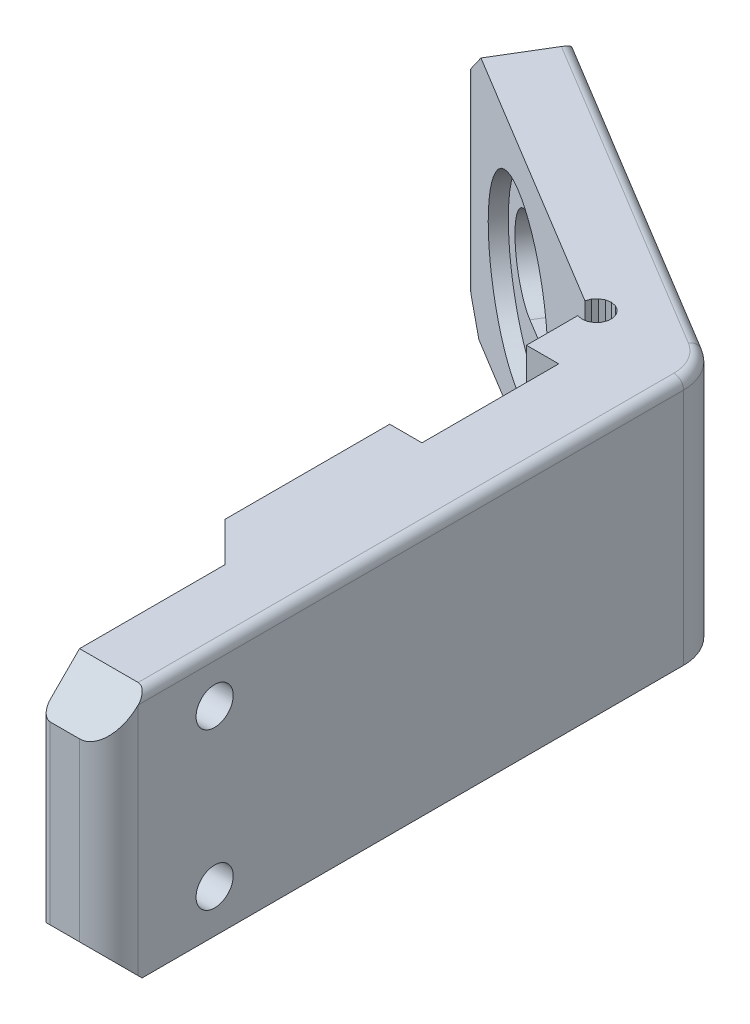
SolidWorks part; units mm, degrees
ref_plane "Front Plane" through (0, 0, 0) normal (0, 0, 1) x (1, 0, 0)
ref_plane "Top Plane" through (0, 0, 0) normal (0, 1, 0) x (1, 0, 0)
ref_plane "Right Plane" through (0, 0, 0) normal (1, 0, 0) x (0, 0, -1)
ref_plane "PY -20.700" through (0, -20.7, 0) normal (0, 1, 0) x (1, 0, 0)
sketch "leg and pad sketch" plane through (0, -20.7, 0) normal (0, 1, 0) x (1, 0, 0)
  line L0 (-0.5513, 30.3327) -> (-0.3673, 30.8194)
  line L1 (-0.3673, 30.8194) -> (-0.028, 31.2139)
  line L2 (-0.028, 31.2139) -> (0.4256, 31.4688)
  line L3 (0.4256, 31.4688) -> (0.939, 31.5534)
  line L4 (0.939, 31.5534) -> (1.4504, 31.4576)
  line L5 (1.4504, 31.4576) -> (1.8983, 31.1928)
  line L6 (1.8983, 31.1928) -> (2.2288, 30.7909)
  line L7 (2.2288, 30.7909) -> (2.4021, 30.3003)
  line L8 (2.4021, 30.3003) -> (2.3973, 29.78)
  line L9 (2.3973, 29.78) -> (2.2152, 29.2926)
  line L10 (2.2152, 29.2926) -> (1.8775, 28.8968)
  line L11 (1.8775, 28.8968) -> (1.4248, 28.6402)
  line L12 (1.4248, 28.6402) -> (0.9118, 28.5536)
  line L13 (0.9118, 28.5536) -> (0.4, 28.6475)
  line L14 (0.4, 28.6475) -> (0.4, -7.48)
  line L15 (0.4, -7.48) -> (4.42, -11.5)
  line L16 (4.42, -11.5) -> (4.42, -30.37)
  line L17 (4.42, -30.37) -> (11.42, -30.37)
  line L18 (11.42, -30.37) -> (11.42, 31.2838)
  line L19 (11.42, 31.2838) -> (-27.2048, 54.5947)
  line L20 (-27.2048, 54.5947) -> (-30.8218, 48.6015)
  line L21 (-30.8218, 48.6015) -> (-0.5513, 30.3327)
extrude "leg and pad" add sketch "leg and pad sketch" along normal mid plane 26
ref_plane "PX 1.350" through (1.35, 0, 0) normal (1, 0, 0) x (0, 0, -1)
sketch "screw head relief sketch" plane through (1.35, 0, 0) normal (1, 0, 0) x (0, 0, -1)
  line L0 (23.4, -12.7) -> (23.4, -6.7)
  line L1 (23.4, -6.7) -> (9.4, -6.7)
  line L2 (9.4, -6.7) -> (9.4, -12.7)
  line L3 (9.4, -12.7) -> (23.4, -12.7)
extrude "screw head relief" cut sketch "screw head relief sketch" against normal mid plane 4.7
sketch "insert flange relief sketch" plane through (0, -20.7, 0) normal (0, 1, 0) x (1, 0, 0)
  line L0 (-18.3249, 39.8914) -> (-17.0331, 42.0318)
  line L1 (-17.0331, 42.0318) -> (-9.3276, 37.3814)
  line L2 (-9.3276, 37.3814) -> (-10.6194, 35.241)
  line L3 (-10.6194, 35.241) -> (-18.3249, 39.8914)
revolve "insert flange relief" cut sketch "insert flange relief sketch" angle 360 about L0
sketch "M6 slot end 1 sketch" plane through (0, -20.7, 0) normal (0, 1, 0) x (1, 0, 0)
  line L0 (-20.4653, 41.1832) -> (-15.8149, 48.8886)
  line L1 (-15.8149, 48.8886) -> (-11.9621, 46.5634)
  line L2 (-11.9621, 46.5634) -> (-16.6125, 38.858)
  line L3 (-16.6125, 38.858) -> (-20.4653, 41.1832)
revolve "M6 slot end 1" cut sketch "M6 slot end 1 sketch" angle 360 about L0
sketch "M6 slot end 2 sketch" plane through (0, -20.7, 0) normal (0, 1, 0) x (1, 0, 0)
  line L0 (-16.1845, 38.5996) -> (-11.5341, 46.3051)
  line L1 (-11.5341, 46.3051) -> (-7.6813, 43.9799)
  line L2 (-7.6813, 43.9799) -> (-12.3317, 36.2744)
  line L3 (-12.3317, 36.2744) -> (-16.1845, 38.5996)
revolve "M6 slot end 2" cut sketch "M6 slot end 2 sketch" angle 360 about L0
sketch "M6 slot middle sketch" plane through (0, -20.7, 0) normal (0, 1, 0) x (1, 0, 0)
  line L0 (-16.1845, 38.5996) -> (-20.4653, 41.1832)
  line L1 (-20.4653, 41.1832) -> (-15.8149, 48.8886)
  line L2 (-15.8149, 48.8886) -> (-11.5341, 46.3051)
  line L3 (-11.5341, 46.3051) -> (-16.1845, 38.5996)
extrude "M6 slot middle" cut sketch "M6 slot middle sketch" against normal mid plane 9
ref_plane "PX 7.920" through (7.92, 0, 0) normal (1, 0, 0) x (0, 0, -1)
sketch "screw holes sketch" plane through (7.92, 0, 0) normal (1, 0, 0) x (0, 0, -1)
  circle A0 centre (-19.54, -28.7) radius 1.9
  circle A1 centre (-19.54, -12.7) radius 1.9
extrude "screw holes" cut sketch "screw holes sketch" against normal mid plane 9
chamfer "leg top corners" distance 4 angle 45 2 edges at (7.92, -7.7, 30.37) (7.92, -33.7, 30.37) tangent propagation no
chamfer "pad end corners" distance 4 angle 45 2 edges at (-29.0133, -7.7, -51.5981) (-29.0133, -33.7, -51.5981) tangent propagation no
fillet "outside of the bend" radius 5 1 edges at (11.42, -20.7, -31.2838) tangent propagation no
fillet "leg top outer edge" radius 3 1 edges at (11.42, -20.7, 30.37) tangent propagation no
fillet "pad end outer edge" radius 3 1 edges at (-27.2048, -20.7, -54.5947) tangent propagation no
fillet "leg top inner edge" radius 1 1 edges at (4.42, -20.7, 30.37) tangent propagation no
fillet "pad end inner edge" radius 1 1 edges at (-30.8218, -20.7, -48.6015) tangent propagation no
chamfer "bed face chamfer" distance 0.6 angle 45 6 edges at (-13.9742, -33.7, -38.4337) (-7.3883, -33.7, -42.635) (4.42, -33.7, 18.935) (0.4, -33.7, -10.5837) (10.7742, -33.7, -30.9193) (11.42, -33.7, -1.0457)
fillet "top face edge" radius 1 3 edges at (-7.3883, -7.7, -42.635) (10.7742, -7.7, -30.9193) (11.42, -7.7, -1.0457)
equation "\"diffL\"= 608.8mm"
equation "\"diffW\"= 329.4mm"
equation "\"diffT\"= 2.9mm"
equation "\"chanSlotW\"= 12.9mm"
equation "\"chanSlotDepth\"= 11.13mm"
equation "\"chanFloor\"= 1.57mm"
equation "\"chanLeg\"= 12.7mm"
equation "\"lightL\"= 605mm"
equation "\"lightW\"= 331mm"
equation "\"lightH\"= 92mm"
equation "\"lightSideFlat\"= 30mm"
equation "\"lightSlopeLen\"= 33.1mm"
equation "\"lightWingDepth\"= 47.9mm"
equation "\"lightWingFlat\"= 90.2mm"
equation "\"lightChanW\"= 99.6mm"
equation "\"lightChanStand\"= 44.1mm"
equation "\"insFlangeD\"= 12.3mm"
equation "\"insFromEnd\"= 20.7mm"
equation "\"insUpSlope\"= 20.8mm"
equation "\"gaugeH\"= 10mm"
equation "\"gaugeStepLen\"= 14mm"
equation "\"gaugeStepW0\"= 13.1mm"
equation "\"gaugeStepDW\"= 0.2mm"
equation "\"gaugeSteps\"= 5mm"
equation "\"gaugeHandleLen\"= 30mm"
equation "\"gaugeHandleW\"= 24mm"
equation "\"gaugeSlot0\"= 3mm"
equation "\"gaugeSlotD\"= 0.1mm"
equation "\"gaugeSlotDepth\"= 8mm"
equation "\"gap\"= 25.4mm"
equation "\"edgeL\"= 1mm"
equation "\"edgeW\"= 0.75mm"
equation "\"proud\"= 1.5mm"
equation "\"seatClr\"= 0.15mm"
equation "\"tongueClrZ\"= 0.1mm"
equation "\"tongueClrX\"= 0.25mm"
equation "\"tongueLen\"= 30mm"
equation "\"armSide\"= 45mm"
equation "\"armEnd\"= 20mm"
equation "\"cornerCham\"= 3mm"
equation "\"brkW\"= 26mm"
equation "\"brkT\"= 7mm"
equation "\"brkSeatClr\"= 0.2mm"
equation "\"brkScrewSpan\"= 16mm"
equation "\"pilotD\"= 2.7mm"
equation "\"pilotDepth\"= 10mm"
equation "\"screwClrD\"= 3.9mm"
equation "\"jogBelow\"= 4mm"
equation "\"padT\"= 7mm"
equation "\"padLen\"= 31mm"
equation "\"m6Clr\"= 7mm"
equation "\"m6Slot\"= 3mm"
equation "\"flangeRelD\"= 17mm"
equation "\"flangeRelDepth\"= 1.5mm"
equation "\"relLen\"= 7mm"
equation "\"relDepth\"= 4mm"
equation "\"relLand\"= 2mm"
equation "\"knockN\"= 100mm"
equation "\"petgcfE\"= 3000mm"
equation "\"mockExtent\"= 110mm"
equation "\"relZnear\"= 9.4mm"
equation "\"relZfar\"= 23.4mm"
equation "\"headD\"= 8mm"
equation "\"headH\"= 2.5mm"
equation "\"headFromEnd\"= 6.8mm"
equation "\"headBack\"= 16.4mm"
equation "\"sideClr\"= 0.4mm"
equation "\"cornerRelR\"= 1.5mm"
equation "\"cornerRelBack\"= 0.6mm"
equation "\"endHeadH\"= 2.8mm"
equation "\"footClr\"= 1.2mm"
equation "\"footEndClr\"= 3.5mm"
equation "\"footLift\"= 6mm"
equation "\"footBlockClr\"= 0.5mm"
equation "\"footBack\"= 50mm"
equation "\"footFwd\"= 10mm"
equation "\"footBraceEnd\"= 3mm"
equation "\"footLoadN\"= 25mm"
equation "\"spacerLen\"= 60mm"
equation "\"spacerShort\"= 0.5mm"
equation "\"spacerCham\"= 0.8mm"
equation "\"spacerPerSide\"= 3mm"
equation "\"spacerPerEnd\"= 1mm"
equation "\"toolR\"= 9mm"
equation "\"visR\"= 4mm"
equation "\"edgeR\"= 1mm"
equation "\"bendOutR\"= 5mm"
equation "\"insideR\"= 2.5mm"
equation "\"footCornerR\"= 10mm"
equation "\"footFrontR\"= 8mm"
equation "\"braceKinkR\"= 12mm"
equation "\"bedCham\"= 1mm"
equation "\"bedChamSmall\"= 0.6mm"
equation "\"soleTopR\"= 2mm"
equation "\"cornerR\"= 6mm"
equation "\"rimInR\"= 1mm"
equation "\"insFlangeH\"= 1mm"
equation "\"insHoleFinishD\"= 4.5mm"
equation "\"insLen\"= 6.4mm"
equation "\"footToeTip\" = 4mm"
equation "\"cgInset\" = 4mm"
equation "\"lampWeightN\" = 51mm"
equation "\"frameWeightN\" = 10mm"
equation "\"bumpIn\" = 8mm"
equation "\"bumpH\" = 3mm"
equation "\"legBelowFront\" = 2mm"
equation "\"lipClr\" = 0.1mm"
equation "\"revealR\" = 2mm"
equation "\"frontCham\" = 1mm"
